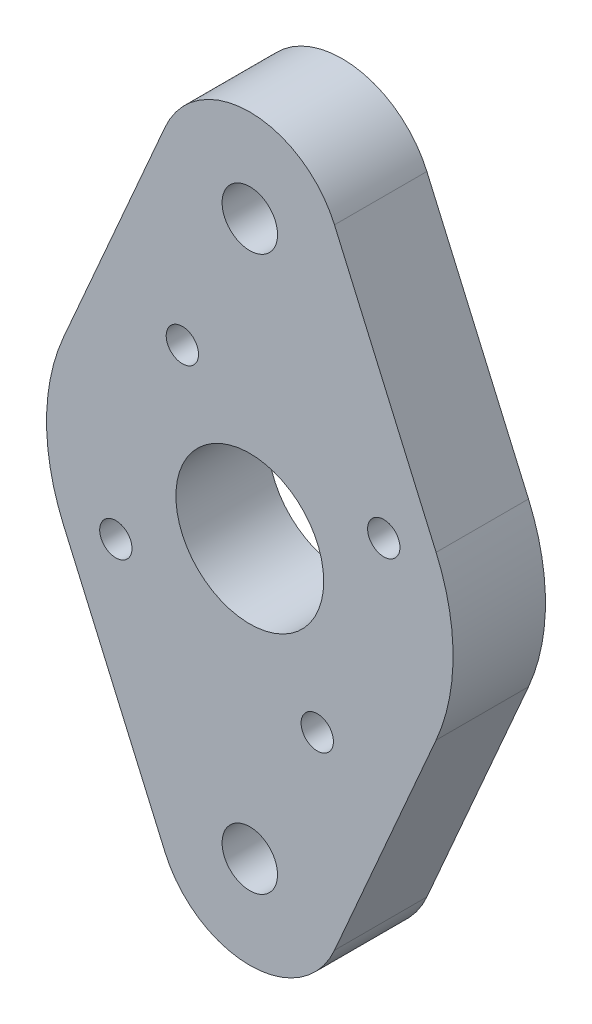
SolidWorks part; units mm, degrees
ref_plane "Plan de face" through (0, 0, 0) normal (0, 0, 1) x (1, 0, 0)
ref_plane "Plan de dessus" through (0, 0, 0) normal (0, 1, 0) x (1, 0, 0)
ref_plane "Plan de droite" through (0, 0, 0) normal (1, 0, 0) x (0, 0, -1)
sketch "Esquisse1" plane through (0, 0, 0) normal (0, 0, 1) x (1, 0, 0)
  line L0 (0, 0) -> (7.25, 0) construction
  line L1 (7.25, 3.65) -> (7.25, 0) construction
  line L2 (0, 0) -> (7.25, 0) construction
  line L3 (0, 0) -> (0, 15) construction
  line L4 (-10.0817, 4.4) -> (-4.5826, 17)
  line L5 (4.5826, 17) -> (10.0817, 4.4)
  line L6 (0, 0) -> (-11, 0) construction
  line L7 (4.5826, -17) -> (10.0817, -4.4)
  line L8 (-10.0817, -4.4) -> (-4.5826, -17)
  circle A0 centre (0, 0) radius 10.5 construction
  circle A1 centre (0, 0) radius 4
  circle A2 centre (7.25, 0) radius 0.875 construction
  circle A3 centre (7.25, 3.65) radius 0.875
  circle A4 centre (7.25, -3.65) radius 0.875 construction
  circle A5 centre (3.65, -7.25) radius 0.875
  circle A6 centre (0, -7.25) radius 0.875 construction
  circle A7 centre (-3.65, -7.25) radius 0.875 construction
  circle A8 centre (-7.25, -3.65) radius 0.875
  circle A9 centre (-7.25, 0) radius 0.875 construction
  circle A10 centre (-7.25, 3.65) radius 0.875 construction
  circle A11 centre (-3.65, 7.25) radius 0.875
  circle A12 centre (0, 7.25) radius 0.875 construction
  circle A13 centre (3.65, 7.25) radius 0.875 construction
  circle A14 centre (0, 15) radius 1.5
  arc A15 (-4.5826, 17) -> (4.5826, 17) centre (0, 15) cw
  arc A16 (-10.0817, -4.4) -> (-10.0817, 4.4) centre (0, 0) cw
  arc A17 (10.0817, -4.4) -> (10.0817, 4.4) centre (0, 0) ccw
  circle A18 centre (0, -15) radius 1.5
  arc A19 (-4.5826, -17) -> (4.5826, -17) centre (0, -15) ccw
  dimension "D1" = 21
  dimension "D2" = 8
  dimension "D5" = 1.75
  dimension "D8" = 5
  dimension "D9" = 11
  dimension "D10" = 3
  dimension "D3" = 7.25
  dimension "D4" = 3.65
  dimension "D7" = 15
  dimension "D6" = 4
extrude "Boss.-Extru.1" add sketch "Esquisse1" along normal blind 5
